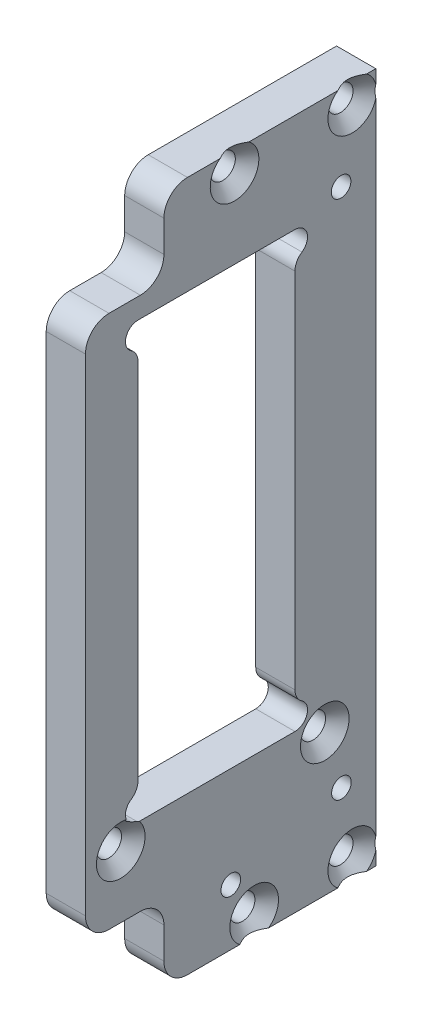
SolidWorks part; units mm, degrees
ref_plane "Front Plane" through (0, 0, 0) normal (1, 0, 0) x (0, 1, 0)
ref_plane "Top Plane" through (0, 0, 0) normal (0, 0, 1) x (0, 1, 0)
ref_plane "Right Plane" through (0, 0, 0) normal (0, 1, 0) x (-1, 0, 0)
sketch "Sketch1" plane through (0, 0, 0) normal (1, 0, 0) x (0, 1, 0)
  line L0 (0, 0) -> (0, -26.7331) construction
  line L1 (-44, 18.5) -> (44, 18.5)
  line L2 (-44, 18.5) -> (-44, -18.5)
  line L3 (-44, -18.5) -> (44, -18.5)
  line L4 (44, 18.5) -> (44, -18.5)
  line L5 (-44, 18.5) -> (44, -18.5) construction
  line L6 (-44, -18.5) -> (44, 18.5) construction
  line L7 (-24, -8.2) -> (-24, 11.8)
  line L8 (-19.4067, 11.8) -> (26.8067, 11.8)
  line L9 (31.4, 11.8) -> (31.4, -8.2)
  line L10 (26.8067, -8.2) -> (-19.4067, -8.2)
  line L11 (-32.5, 12.8) -> (-32.5, -9.2) construction
  line L12 (-32.5, 1.8) -> (31.4, 1.8) construction
  line L13 (-24, 1.8) -> (-30, 1.8) construction
  circle A1 centre (-41.5, -15.5) radius 1.6
  circle A2 centre (-41.5, -3) radius 1.6
  circle A4 centre (41.5, -15.5) radius 1.6
  circle A5 centre (-26, 14) radius 1.6
  circle A6 centre (-26, -12) radius 1.6
  arc A10 (-21.0696, 12.6889) -> (-24, 11.8) centre (-22.4, 11.8) ccw
  arc A11 (-21.0696, 12.6889) -> (-19.4067, 11.8) centre (-19.4067, 13.8) ccw
  arc A12 (28.4696, 12.6889) -> (26.8067, 11.8) centre (26.8067, 13.8) cw
  arc A13 (28.4696, 12.6889) -> (31.4, 11.8) centre (29.8, 11.8) cw
  arc A14 (28.4696, -9.0889) -> (31.4, -8.2) centre (29.8, -8.2) ccw
  arc A15 (28.4696, -9.0889) -> (26.8067, -8.2) centre (26.8067, -10.2) ccw
  arc A16 (-21.0696, -9.0889) -> (-19.4067, -8.2) centre (-19.4067, -10.2) cw
  arc A17 (-21.0696, -9.0889) -> (-24, -8.2) centre (-22.4, -8.2) cw
  circle A18 centre (41.5, -0.5) radius 1.6
  point P0 (0, 0)
  dimension "D3" = 3.2
  dimension "D4" = 3
  dimension "D5" = 3.2
  dimension "D10" = 3.2
  dimension "D11" = 3.2
  dimension "D8" = 2.5
  dimension "D16" = 20
  dimension "D14" = 18
  dimension "D13" = 26
  dimension "D17" = 15
  dimension "D1" = 37
  dimension "D2" = 88
  dimension "D6" = 12.5
  dimension "D7" = 2.5
  dimension "D9" = 15.5
  dimension "D12" = 4.5
  dimension "D15" = 6.7
  dimension "D18" = 0
extrude "Boss-Extrude1" add sketch "Sketch1" along normal blind 5
fillet "Fillet1" radius 5 2 edges at (2.5, 44, 18.5) (2.5, -44, 18.5)
chamfer "Chamfer2" distance 1.5 angle 45 6 edges at (5, -26, 12.4) (5, -26, -13.6) (5, -41.5, -17.1) (5, -41.5, -4.6) (5, 41.5, -13.9) (5, 41.5, -2.1)
sketch "Sketch2" plane through (5, 0, 0) normal (1, 0, 0) x (0, 1, 0)
  circle A0 centre (-36.8266, -0.0231) radius 1.25
  circle A1 centre (-33.1674, -14.1207) radius 1.25
  circle A2 centre (33.1826, -14.0775) radius 1.25
extrude "Cut-Extrude1" cut sketch "Sketch2" against normal blind 10
sketch "Sketch3" plane through (5, 0, 0) normal (1, 0, 0) x (0, 1, 0)
  line L0 (-44, 8.5) -> (-34, 8.5)
  line L1 (-44, 13.5) -> (-44, -1.167) construction
  line L2 (-34, 8.5) -> (-34, 18.5)
  line L3 (39, 18.5) -> (-39, 18.5) construction
  line L4 (0, 0) -> (0, 27.0498) construction
  line L5 (44, 8.5) -> (34, 8.5)
  line L6 (34, 8.5) -> (34, 18.5)
  line L7 (-44, 8.5) -> (-44, 18.5)
  line L8 (-44, 18.5) -> (-34, 18.5)
  line L9 (44, 8.5) -> (44, 18.5)
  line L10 (44, 18.5) -> (34, 18.5)
  dimension "D1" = 10
  dimension "D2" = 10
extrude "Cut-Extrude2" cut sketch "Sketch3" against normal blind 10
fillet "Fillet2" radius 3 6 edges at (2.5, -34, 18.5) (2.5, -34, 8.5) (2.5, -44, 8.5) (2.5, 34, 18.5) (2.5, 34, 8.5) (2.5, 44, 8.5)
